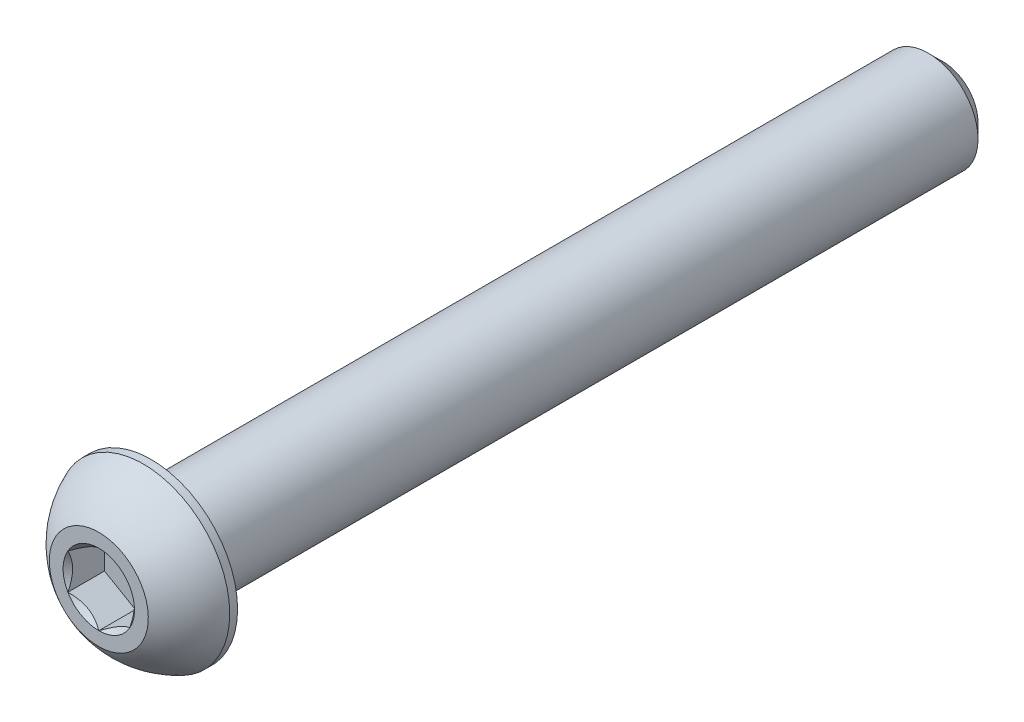
SolidWorks part; units mm, degrees
material "Wrought Stainless Steel"
ref_plane "Front" through (0, 0, 0) normal (0, 0, 1) x (1, 0, 0)
ref_plane "Top" through (0, 0, 0) normal (0, 1, 0) x (1, 0, 0)
ref_plane "Right" through (0, 0, 0) normal (1, 0, 0) x (0, 0, -1)
sketch "Sketch1" plane through (0, 0, 0) normal (1, 0, 0) x (0, 0, -1)
  line L2 (3.3528, 3.175) -> (54.1528, 3.175)
  line L3 (54.1528, 3.175) -> (54.1528, 0)
  line L4 (54.1528, 0) -> (3.3528, 0)
  line L6 (2.8499, 5.5499) -> (3.3528, 5.5499) construction
  line L7 (54.1528, 3.175) -> (54.1528, -3.175) construction
  line L8 (0, 0) -> (3.3528, 0) construction
  line L9 (3.3528, 5.5499) -> (3.3528, -5.5499) construction
  line L11 (3.3528, 3.175) -> (3.3528, 0)
  line L13 (0, 1.9844) -> (0, -1.9844) construction
  line L14 (0, 1.9844) -> (0, 3.175) construction
  arc A3 (0, 3.175) -> (2.8499, 5.5499) centre (5.0603, 0) cw construction
  dimension "D1" = 0.5029
revolve "Revolve1" add sketch "Sketch1" angle 360 mid plane about L4
sketch "Sketch3" plane through (0, 0, -54.1528) normal (0, 0, -1) x (-1, 0, 0)
  circle A0 centre (0, 0) radius 3.175
curve "Helix/Spiral1" pitch 1.239 height 54.1528 turns 43.706
sketch "Sketch2" plane through (0, 0, 0) normal (1, 0, 0) x (0, 0, -1)
  line L0 (54.1528, 3.175) -> (55.2369, 3.175)
  line L1 (55.2369, 3.175) -> (54.7723, 2.3702)
  line L2 (54.7723, 2.3702) -> (54.6174, 2.3702)
  line L3 (54.6174, 2.3702) -> (54.1528, 3.175)
  line L4 (54.3851, 2.7726) -> (55.0046, 2.7726) construction
  dimension "D1" = 60
  dimension "D2" = 0.1549
  dimension "D3" = 0.6195
chamfer "Chamfer1" distance 0.9293 angle 45 1 edges at (0, 3.175, -54.1528)
sweep "Cut-Sweep1" [suppressed] cut profiles "Sketch2" path "Helix/Spiral1"
sketch "Sketch7" plane through (0, 0, 0) normal (1, 0, 0) x (0, 0, -1)
  line L6 (2.8499, 5.5499) -> (3.3528, 5.5499) construction
  line L8 (0, 0) -> (3.3528, 0) construction
  line L11 (3.3528, 5.5499) -> (3.3528, -5.5499) construction
  line L12 (2.8499, 5.5499) -> (3.3528, 5.5499)
  line L13 (0, 0) -> (3.3528, 0)
  line L14 (0, 1.9844) -> (0, -1.9844) construction
  line L15 (3.3528, 5.5499) -> (3.3528, 0)
  line L16 (0, 3.175) -> (0, 0)
  arc A2 (2.8499, 5.5499) -> (0, 3.175) centre (5.0603, 0) ccw construction
  arc A3 (2.8499, 5.5499) -> (0, 3.175) centre (5.0603, 0) ccw
revolve "Revolve2" add sketch "Sketch7" angle 360 mid plane about L13
sketch "Sketch5" plane through (0, 0, 0) normal (0, 0, 1) x (1, 0, 0)
  line L1 (1.9844, -1.1457) -> (1.9844, 1.1457)
  line L2 (1.9844, 1.1457) -> (0, 2.2914)
  line L3 (0, 2.2914) -> (-1.9844, 1.1457)
  line L4 (-1.9844, 1.1457) -> (-1.9844, -1.1457)
  line L5 (-1.9844, -1.1457) -> (0, -2.2914)
  line L6 (0, -2.2914) -> (1.9844, -1.1457)
  circle A0 centre (0, 0) radius 1.9844 construction
extrude "Cut-Extrude2" cut sketch "Sketch5" against normal blind 2.347
sketch "Sketch6" plane through (0, 0, 0) normal (0, 0, 1) x (1, 0, 0)
  circle A0 centre (0, 0) radius 2.2914
extrude "Cut-Extrude3" cut sketch "Sketch6" against normal blind 2.347 draft 45
sketch "Sketch9" [suppressed] plane through (0, 0, -3.3528) normal (0, 0, 1) x (1, 0, 0)
  circle A2 centre (0, 0) radius 3.175
extrude "Boss-Extrude2" [suppressed] add sketch "Sketch9" against normal offset from surface (25.4 mm away) 25.4
sketch "Sketch10" plane through (0, 0, 0) normal (1, 0, 0) x (0, 0, -1)
  line L0 (54.1528, 3.175) -> (54.1528, -3.175) construction
  point P0 (52.2943, -3.175)
  dimension "D1" = 1.8585
equation "\"D3@Helix/Spiral1\" = \"Lg@Sketch1\" + \"Head Ht@Sketch1\""
equation "\"D2@Sketch2\" = \"D4@Helix/Spiral1\" * .125"
equation "\"D3@Sketch2\" = \"D4@Helix/Spiral1\" * .5"
equation "\"D1@Chamfer1\" = \"D4@Helix/Spiral1\" * .75"
equation "\"D1@Cut-Extrude2\" = \"Head Ht@Sketch1\" * .7"
equation "\"D1@Sketch1\" = \"Head Ht@Sketch1\" * .15"
equation "\"D1@Sketch10\" = \"D4@Helix/Spiral1\" * 1.5"
equation "\"D1@Cut-Extrude3\" = \"D1@Cut-Extrude2\""
